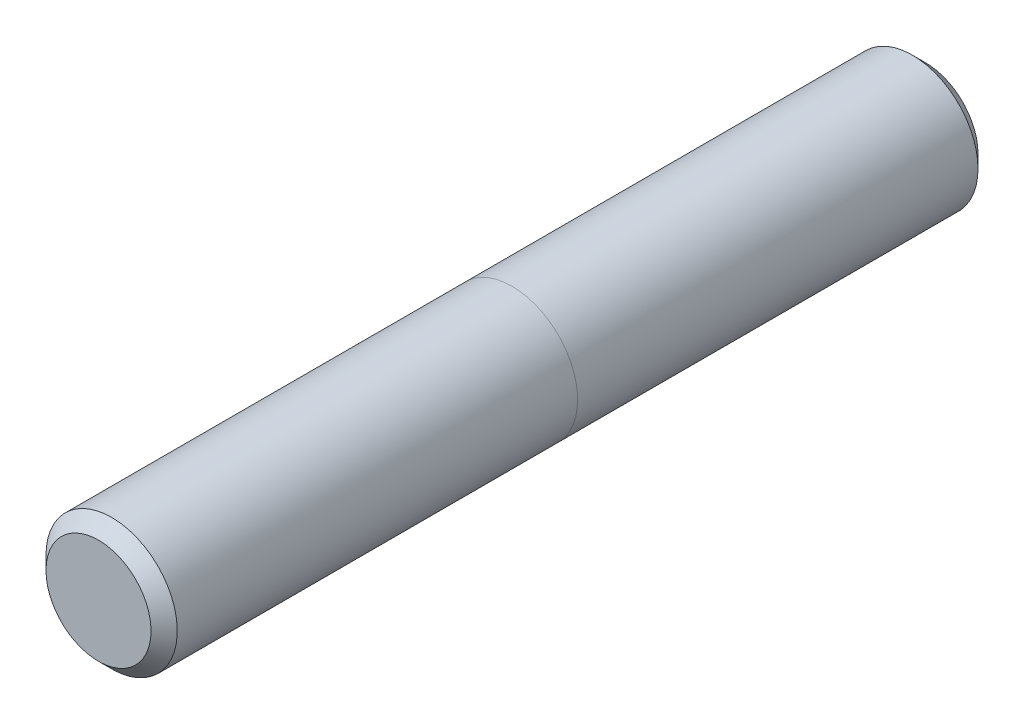
SolidWorks part; units mm, degrees
material "Plain Carbon Steel"
ref_plane "Front" through (0, 0, 0) normal (0, 0, 1) x (1, 0, 0)
ref_plane "Top" through (0, 0, 0) normal (0, 1, 0) x (1, 0, 0)
ref_plane "Right" through (0, 0, 0) normal (1, 0, 0) x (0, 0, -1)
sketch "Sketch1" plane through (0, 0, 0) normal (0, 0, 1) x (1, 0, 0)
  circle A0 centre (0, 0) radius 7.9375
  dimension "Diameter" = 15.875
sketch "Sketch2" plane through (0, 0, 0) normal (1, 0, 0) x (0, 0, -1)
  line L0 (-50, 0) -> (50, 0) construction
  line L1 (0.8, 7.9375) -> (0.8, -7.9375) construction
  line L2 (8.7312, 0) -> (-8.7312, 0) construction
  line L3 (-0.8, 7.9375) -> (-0.8, -7.9375) construction
  line L4 (-50, 7.9375) -> (-50, -7.9375) construction
  line L5 (50, 7.9375) -> (50, -7.9375) construction
  point P3 (0.8, 0)
  point P8 (0, 0)
  point P9 (-0.8, 0)
  point P15 (-50, 0)
  point P18 (50, 0)
  dimension "D1" = 15.875
  dimension "Length" = 100
  dimension "D2" = 50.8
  dimension "D3" = 50.8
sketch "Sketch3" plane through (0, 0, 0) normal (0, 0, 1) x (1, 0, 0)
  circle A0 centre (0, 0) radius 7.9375
  dimension "D1" = 15.875
extrude "Boss-Extrude1" add sketch "Sketch3" along normal mid plane 100
chamfer "Chamfer1" distance 1.5875 angle 45 2 edges at (7.9375, 0, -50) (7.9375, 0, 50)
sketch "Sketch5" plane through (0, 0, 0) normal (0, 1, 0) x (1, 0, 0)
  line L0 (-7.9375, 0) -> (7.9375, 0)
  line L1 (-7.9375, 48.4125) -> (-7.9375, -48.4125) construction
  line L2 (7.9375, -48.4125) -> (7.9375, 48.4125) construction
  line L4 (-6.35, -50) -> (6.35, -50) construction
  dimension "D1" = 50
split line "Split Line1"
equation "\"D1@Sketch3\" = \"Diameter@Sketch1\""
equation "\"D1@Boss-Extrude1\" = \"Length@Sketch2\""
equation "\"D1@Chamfer1\" = \"Diameter@Sketch1\" * .1"
equation "\"D1@Sketch2\" = \"Diameter@Sketch1\""
